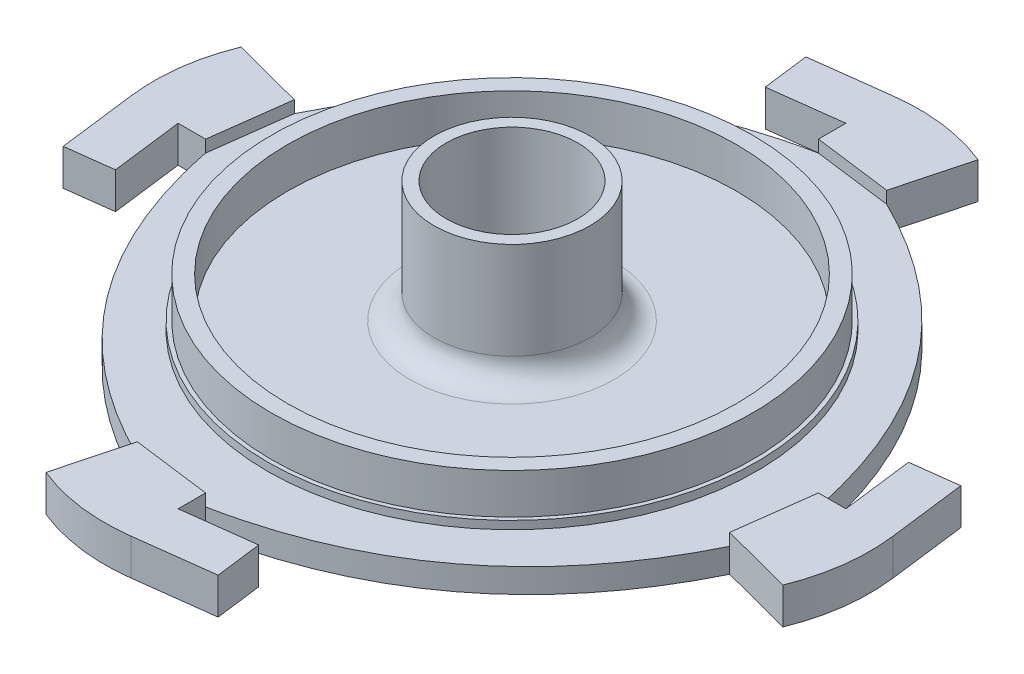
SolidWorks part; units mm, degrees
ref_plane "Front Plane" through (0, 0, 0) normal (0, 0, 1) x (1, 0, 0)
ref_plane "Top Plane" through (0, 0, 0) normal (0, 1, 0) x (1, 0, 0)
ref_plane "Right Plane" through (0, 0, 0) normal (1, 0, 0) x (0, 0, -1)
sketch "Sketch1" plane through (0, 0, 0) normal (0, 1, 0) x (1, 0, 0)
  line L5 (-36.6847, 9.718) -> (-45.6262, 12.0866)
  line L7 (0, 37.95) -> (9.718, 36.6847)
  line L8 (-36.6847, 9.718) -> (-37.95, 0)
  line L9 (36.6847, -9.718) -> (37.95, 0)
  line L10 (0, -37.95) -> (-9.718, -36.6847)
  line L12 (9.718, 36.6847) -> (12.0866, 45.6262)
  line L16 (36.6847, -9.718) -> (45.6262, -12.0866)
  line L20 (-9.718, -36.6847) -> (-12.0866, -45.6262)
  line L22 (0, 47.2) -> (-9.5942, 45.9919)
  line L23 (-9.5942, 45.9919) -> (-8.8696, 40.2373)
  line L24 (-8.8696, 40.2373) -> (0, 41.3542)
  line L25 (0, 41.3542) -> (0, 37.95)
  line L26 (-47.2, 0) -> (-45.9919, -9.5942)
  line L27 (-45.9919, -9.5942) -> (-40.2373, -8.8696)
  line L28 (-40.2373, -8.8696) -> (-41.3542, 0)
  line L29 (-41.3542, 0) -> (-37.95, 0)
  line L30 (0, -47.2) -> (9.5942, -45.9919)
  line L31 (9.5942, -45.9919) -> (8.8696, -40.2373)
  line L32 (8.8696, -40.2373) -> (0, -41.3542)
  line L33 (0, -41.3542) -> (0, -37.95)
  line L34 (47.2, 0) -> (45.9919, 9.5942)
  line L35 (45.9919, 9.5942) -> (40.2373, 8.8696)
  line L36 (40.2373, 8.8696) -> (41.3542, 0)
  line L37 (41.3542, 0) -> (37.95, 0)
  spline S0 degree 2 poles (-36.6847, 9.718) (-25.3257, 32.9081) (0, 37.95) knots 0 0 0 1 1 1
  spline S1 degree 2 poles (9.718, 36.6847) (32.9081, 25.3257) (37.95, 0) knots 0 0 0 1 1 1
  spline S2 degree 2 poles (36.6847, -9.718) (25.3257, -32.9081) (0, -37.95) knots 0 0 0 1 1 1
  spline S3 degree 2 poles (-9.718, -36.6847) (-32.9081, -25.3257) (-37.95, 0) knots 0 0 0 1 1 1
  spline S4 degree 3 poles (12.0866, 45.6262) (8.1944, 47.2001) (4.1655, 47.7245) (0, 47.2) knots 0 0 0 0 1 1 1 1
  spline S5 degree 3 poles (-45.6262, 12.0866) (-47.2001, 8.1944) (-47.7245, 4.1655) (-47.2, 0) knots 0 0 0 0 1 1 1 1
  spline S6 degree 3 poles (-12.0866, -45.6262) (-8.1944, -47.2001) (-4.1655, -47.7245) (0, -47.2) knots 0 0 0 0 1 1 1 1
  spline S7 degree 3 poles (47.2, 0) (47.7245, -4.1655) (47.2001, -8.1944) (45.6262, -12.0866) knots 0 0 0 0 1 1 1 1
  point P12 (-21.834, 28.3711)
  point P14 (-28.3711, -21.834)
  point P15 (-34.6063, 9.1674)
  point P18 (21.834, -28.3711)
  point P19 (-35.8, 0)
  point P20 (-9.1674, -34.6063)
  point P21 (0, -35.8)
  point P22 (34.6063, -9.1674)
  point P23 (35.8, 0)
  point P24 (0, 35.8)
  point P25 (9.1674, 34.6063)
  point P27 (28.3711, 21.834)
  point P41 (6.1458, 47.2)
  point P43 (6.1458, 47.2)
  point P44 (6.1458, 47.2)
  point P45 (-47.2, 6.1458)
  point P46 (-6.1458, -47.2)
  point P47 (47.2, -6.1458)
  dimension "D1" = 9.8
  dimension "D2" = 9.25
  dimension "D3" = 9.25
  dimension "D13" = 12.3251
  dimension "D14" = 12.3251
  dimension "D15" = 12.3251
  dimension "D16" = 12.3251
  dimension "D4" = 9.8
  dimension "D5" = 9.25
  dimension "D6" = 9.25
  dimension "D7" = 9.25
  dimension "D8" = 9.25
  dimension "D11" = 9.25
  dimension "D12" = 9.25
  dimension "D17" = 9.67
  dimension "D18" = 9.67
  dimension "D19" = 9.67
  dimension "D20" = 9.67
  dimension "D21" = 5.8
  dimension "D22" = 5.8
  dimension "D23" = 5.8
  dimension "D24" = 5.8
extrude "Boss-Extrude1" add sketch "Sketch1" along normal blind 3 contours S3 L10 S2 L9 S1 L7 S0 L8 | L5 S5 L26 L27 L28 L29 L8 | L20 S6 L30 L31 L32 L33 L10 | S7 L34 L35 L36 L37 L9 L16 | L12 S4 L22 L23 L24 L25 L7 region at (-42.788, 0, -2.12) region at (0, 0, 0) region at (2.12, 0, -42.788) region at (-2.12, 0, 42.788) region at (42.788, 0, 2.12)
extrude "Boss-Extrude2" add sketch "Sketch1<3>" along normal blind 1.5 from surface contours L20 S6 L30 L31 L32 L33 L10 | S7 L34 L35 L36 L37 L9 L16 | L12 S4 L22 L23 L24 L25 L7 | L5 S5 L26 L27 L28 L29 L8 region at (-42.788, 0, -2.12) region at (2.12, 0, -42.788) region at (-2.12, 0, 42.788) region at (42.788, 0, 2.12) starting at face at (0.0562, 3, -0.4317)
sketch "Sketch1<3>" plane through (0, 0, 0) normal (0, 1, 0) x (1, 0, 0) same geometry as "Sketch1"
sketch "Sketch2" plane through (0, 3, 0) normal (0, 1, 0) x (1, 0, 0)
  circle A0 centre (0, 0) radius 29.8
  circle A1 centre (0, 0) radius 30.3
  circle A2 centre (0, 0) radius 27.8
  dimension "D1" = 59.6
  dimension "D2" = 60.6
  dimension "D3" = 55.6
extrude "Boss-Extrude3" add sketch "Sketch2" along normal blind 1 contours A1 A0 | A0 A2 | A2 region at (-28.9571, 3, 0) region at (-30.2143, 3, 0) region at (0, 3, 0)
sketch "Sketch3" plane through (0, 4, 0) normal (0, 1, 0) x (1, 0, 0)
  circle A0 centre (0, 0) radius 27.8
  circle A1 centre (0, 0) radius 29.8
  dimension "D1" = 55.6
  dimension "D2" = 59.6
extrude "Boss-Extrude4" add sketch "Sketch3" along normal blind 5
sketch "Sketch4" plane through (0, 4, 0) normal (0, 1, 0) x (1, 0, 0)
  circle A0 centre (0, 0) radius 8.15
  circle A1 centre (0, 0) radius 9.65
  dimension "D1" = 16.3
  dimension "D2" = 19.3
extrude "Boss-Extrude5" add sketch "Sketch4" along normal blind 15
fillet "Fillet1" radius 3 1 edges at (0, 4, 9.65)
sketch "Sketch5" plane through (0, 0, 0) normal (0, -1, 0) x (1, 0, 0)
  circle A0 centre (0, 0) radius 8.15
  dimension "D1" = 16.3
extrude "Cut-Extrude1" cut sketch "Sketch5" against normal blind 19
